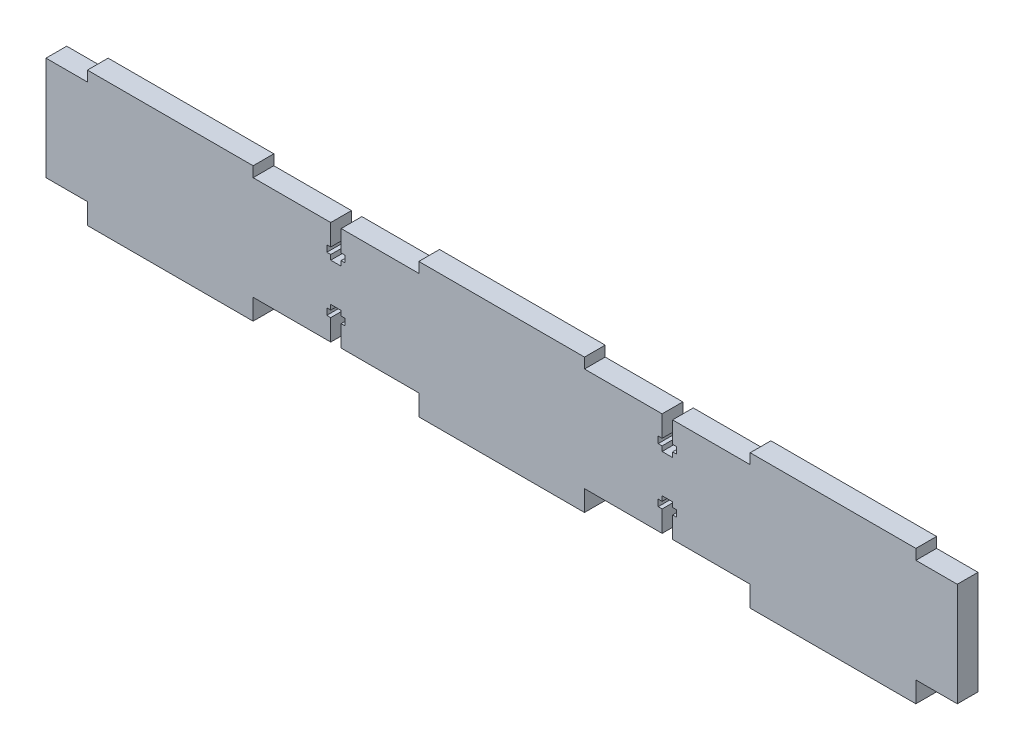
SolidWorks part; units mm, degrees
ref_plane "Front Plane" through (0, 0, 0) normal (0, 0, 1) x (1, 0, 0)
ref_plane "Top Plane" through (0, 0, 0) normal (0, 1, 0) x (1, 0, 0)
ref_plane "Right Plane" through (0, 0, 0) normal (1, 0, 0) x (0, 0, -1)
sketch "Sketch1" plane through (0, 0, 0) normal (0, 0, 1) x (1, 0, 0)
  line L0 (63.5, -3.175) -> (114.3, -3.175) construction
  line L1 (0, 0) -> (12.7, 0)
  line L2 (0, 0) -> (0, 31.75)
  line L3 (0, 31.75) -> (12.7, 31.75)
  line L4 (279.4, 0) -> (279.4, 31.75)
  line L5 (0, 15.875) -> (279.4, 15.875) construction
  line L6 (12.7, 0) -> (12.7, -6.35)
  line L7 (12.7, -6.35) -> (63.5, -6.35)
  line L8 (63.5, 0) -> (63.5, -6.35)
  line L9 (63.5, 0) -> (114.3, 0)
  line L10 (114.3, 0) -> (114.3, -6.35)
  line L11 (114.3, -6.35) -> (165.1, -6.35)
  line L12 (165.1, 0) -> (165.1, -6.35)
  line L13 (165.1, 0) -> (215.9, 0)
  line L14 (215.9, 0) -> (215.9, -6.35)
  line L15 (215.9, -6.35) -> (266.7, -6.35)
  line L16 (266.7, 0) -> (266.7, -6.35)
  line L17 (165.1, 31.75) -> (215.9, 31.75)
  line L18 (12.7, 31.75) -> (12.7, 34.925)
  line L19 (12.7, 34.925) -> (63.5, 34.925)
  line L20 (63.5, 31.75) -> (63.5, 34.925)
  line L21 (266.7, 31.75) -> (279.4, 31.75)
  line L22 (114.3, 31.75) -> (114.3, 34.925)
  line L23 (114.3, 34.925) -> (165.1, 34.925)
  line L24 (165.1, 31.75) -> (165.1, 34.925)
  line L25 (266.7, 0) -> (279.4, 0)
  line L26 (215.9, 31.75) -> (215.9, 34.925)
  line L27 (215.9, 34.925) -> (266.7, 34.925)
  line L28 (266.7, 31.75) -> (266.7, 34.925)
  line L29 (165.1, -3.175) -> (215.9, -3.175) construction
  line L30 (165.1, 33.3375) -> (215.9, 33.3375) construction
  line L31 (63.5, 33.3375) -> (114.3, 33.3375) construction
  line L32 (12.7, 33.3375) -> (0, 33.3375) construction
  line L33 (12.7, -3.175) -> (0, -3.175) construction
  line L34 (266.7, 33.3375) -> (279.4, 33.3375) construction
  line L35 (266.7, -3.175) -> (279.4, -3.175) construction
  line L36 (63.5, 31.75) -> (114.3, 31.75)
  line L37 (139.7, 34.925) -> (139.7, -6.35) construction
  line L38 (88.9, 31.75) -> (88.9, 0) construction
  dimension "D1" = 279.4
  dimension "D2" = 31.75
  dimension "D3" = 3.175
  dimension "D4" = 6.35
  dimension "D5" = 50.8
extrude "BaseExtrude" add sketch "Sketch1" along normal blind 6.35
sketch "Sketch2" plane through (0, 0, 6.35) normal (0, 0, 1) x (1, 0, 0)
  line L0 (88.9, 31.75) -> (88.9, 0) construction
  line L1 (114.3, 31.75) -> (63.5, 31.75) construction
  line L2 (63.5, 0) -> (114.3, 0) construction
  line L3 (0, 15.875) -> (279.4, 15.875) construction
  line L4 (0, 31.75) -> (0, 0) construction
  line L5 (279.4, 0) -> (279.4, 31.75) construction
  line L6 (86.1, 24.25) -> (91.7, 24.25) construction
  line L7 (90.5, 31.75) -> (87.3, 31.75)
  line L8 (90.5, 31.75) -> (90.5, 25.25)
  line L9 (90.5, 21.75) -> (87.3, 21.75)
  line L10 (87.3, 31.75) -> (87.3, 25.25)
  line L11 (86.1, 25.25) -> (87.3, 25.25)
  line L12 (86.1, 25.25) -> (86.1, 23.25)
  line L13 (86.1, 23.25) -> (87.3, 23.25)
  line L14 (86.1, 7.5) -> (91.7, 7.5) construction
  line L15 (90.5, 25.25) -> (91.7, 25.25)
  line L16 (90.5, 23.25) -> (90.5, 21.75)
  line L17 (90.5, 23.25) -> (91.7, 23.25)
  line L18 (91.7, 25.25) -> (91.7, 23.25)
  line L19 (87.3, 23.25) -> (87.3, 21.75)
  line L20 (87.3, 8.5) -> (87.3, 10)
  line L21 (91.7, 6.5) -> (91.7, 8.5)
  line L22 (90.5, 8.5) -> (91.7, 8.5)
  line L23 (90.5, 8.5) -> (90.5, 10)
  line L24 (90.5, 6.5) -> (91.7, 6.5)
  line L25 (86.1, 8.5) -> (87.3, 8.5)
  line L26 (86.1, 6.5) -> (86.1, 8.5)
  line L27 (86.1, 6.5) -> (87.3, 6.5)
  line L28 (87.3, 0) -> (87.3, 6.5)
  line L29 (90.5, 10) -> (87.3, 10)
  line L30 (90.5, 0) -> (90.5, 6.5)
  line L31 (90.5, 0) -> (87.3, 0)
  line L32 (139.7, 34.925) -> (139.7, -6.35) construction
  line L33 (165.1, 34.925) -> (114.3, 34.925) construction
  line L34 (114.3, -6.35) -> (165.1, -6.35) construction
  line L35 (193.3, 7.5) -> (187.7, 7.5) construction
  line L36 (193.3, 24.25) -> (187.7, 24.25) construction
  line L37 (188.9, 0) -> (192.1, 0)
  line L38 (188.9, 0) -> (188.9, 6.5)
  line L39 (188.9, 10) -> (192.1, 10)
  line L40 (192.1, 0) -> (192.1, 6.5)
  line L41 (193.3, 6.5) -> (192.1, 6.5)
  line L42 (193.3, 6.5) -> (193.3, 8.5)
  line L43 (193.3, 8.5) -> (192.1, 8.5)
  line L44 (188.9, 6.5) -> (187.7, 6.5)
  line L45 (188.9, 8.5) -> (188.9, 10)
  line L46 (188.9, 8.5) -> (187.7, 8.5)
  line L47 (187.7, 6.5) -> (187.7, 8.5)
  line L48 (192.1, 8.5) -> (192.1, 10)
  line L49 (192.1, 23.25) -> (192.1, 21.75)
  line L50 (187.7, 25.25) -> (187.7, 23.25)
  line L51 (188.9, 23.25) -> (187.7, 23.25)
  line L52 (188.9, 23.25) -> (188.9, 21.75)
  line L53 (188.9, 25.25) -> (187.7, 25.25)
  line L54 (193.3, 23.25) -> (192.1, 23.25)
  line L55 (193.3, 25.25) -> (193.3, 23.25)
  line L56 (193.3, 25.25) -> (192.1, 25.25)
  line L57 (192.1, 31.75) -> (192.1, 25.25)
  line L58 (188.9, 21.75) -> (192.1, 21.75)
  line L59 (188.9, 31.75) -> (188.9, 25.25)
  line L60 (188.9, 31.75) -> (192.1, 31.75)
  point P24 (88.9, 21.75)
  dimension "D1" = 2
  dimension "D2" = 5.6
  dimension "D3" = 3.2
  dimension "D4" = 10
  dimension "D5" = 7.5
extrude "ScrewCuts" cut sketch "Sketch2" against normal through all
